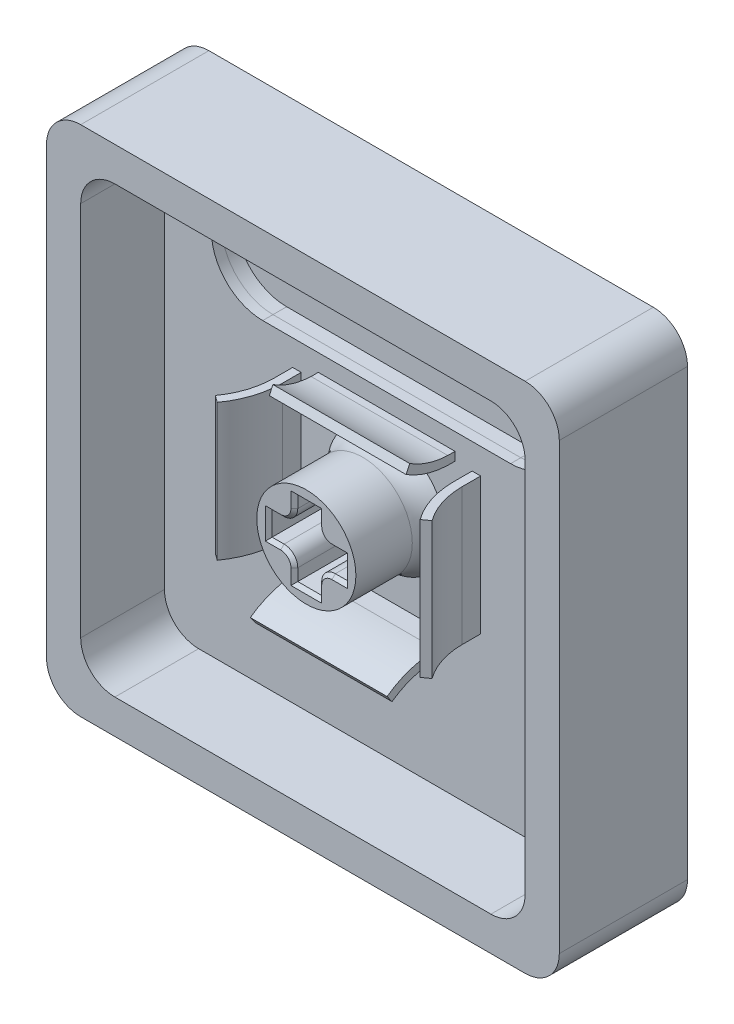
SolidWorks part; units mm, degrees
note: '?' marks a value the reader was unsure of. The reader was unsure of these and kept them because the rebuilt part matched: shared geometry of "草图1<6>", "草图1<7>".
other "标注1"
sketch "草图2" plane through (15, -15, 10) normal (0.3933, -0.7926, 0.466) x (0.9059, 0.4207, -0.0491)
ref_plane "前视基准面" through (0, 0, 0) normal (0, 0, 1) x (1, 0, 0)
ref_plane "上视基准面" through (0, 0, 0) normal (0, 1, 0) x (1, 0, 0)
ref_plane "右视基准面" through (0, 0, 0) normal (1, 0, 0) x (0, 0, -1)
sketch "草图1" plane through (0, 0, 0) normal (0, 0, 1) x (1, 0, 0)
  line L0 (-13, 15) -> (13, 15)
  line L1 (-11, 13) -> (11, 13)
  line L2 (-13, 11) -> (-13, -11)
  line L3 (-11, -13) -> (11, -13)
  line L4 (13, 11) -> (13, -11)
  line L5 (0, -13) -> (0, 13) construction
  line L6 (-13, 0) -> (13, 0) construction
  line L7 (15, 13) -> (15, -13)
  line L8 (-13, -15) -> (13, -15)
  line L9 (-15, 13) -> (-15, -13)
  line L10 (-13, -13) -> (13, -13) construction
  line L11 (-2.2, 0.7) -> (2.2, 0.7)
  line L12 (-2.2, 0.7) -> (-2.2, -0.7)
  line L13 (-2.2, -0.7) -> (2.2, -0.7)
  line L14 (2.2, 0.7) -> (2.2, -0.7)
  line L15 (0, -0.7) -> (0, 0.7) construction
  line L16 (-2.2, 0) -> (2.2, 0) construction
  line L17 (-0.7, 2.2) -> (0.7, 2.2)
  line L18 (-0.7, 2.2) -> (-0.7, -2.2)
  line L19 (-0.7, -2.2) -> (0.7, -2.2)
  line L20 (0.7, 2.2) -> (0.7, -2.2)
  line L21 (0, -2.2) -> (0, 2.2) construction
  line L22 (-0.7, 0) -> (0.7, 0) construction
  line L23 (13, 13) -> (13, -13) construction
  line L24 (-13, 13) -> (13, 13) construction
  line L25 (-13, 13) -> (-13, -13) construction
  line L26 (-15, 15) -> (-15, -15) construction
  line L27 (-15, -15) -> (15, -15) construction
  line L28 (15, 15) -> (15, -15) construction
  line L29 (-15, 15) -> (15, 15) construction
  line L36 (-13, 0) -> (-2.5, 0) construction
  circle A0 centre (0, 0) radius 2.9
  arc A1 (11, -13) -> (13, -11) centre (11, -11) ccw
  arc A2 (13, 11) -> (11, 13) centre (11, 11) ccw
  arc A3 (-13, 11) -> (-11, 13) centre (-11, 11) cw
  arc A4 (-13, -11) -> (-11, -13) centre (-11, -11) ccw
  arc A5 (-15, -13) -> (-13, -15) centre (-13, -13) ccw
  arc A6 (13, -15) -> (15, -13) centre (13, -13) ccw
  arc A7 (15, 13) -> (13, 15) centre (13, 13) ccw
  arc A8 (-15, 13) -> (-13, 15) centre (-13, 13) cw
  point P0 (0, 0)
  point P19 (13, -13)
  point P66 (0.0162, 0.0162)
  dimension "D4" = 5.8
  dimension "D9" = 2
  dimension "D1" = 30
  dimension "D2" = 30
  dimension "D5" = 4.4
  dimension "D6" = 1.4
  dimension "D7" = 4.4
  dimension "D8" = 1.4
  dimension "D3" = 2
extrude "凸台-拉伸1" add sketch "草图1" along normal blind 5.5 contours A8 L9 A5 L8 A6 L7 A7 L0 A4 L2 A3 L1 A2 L4 A1 L3
extrude "凸台-拉伸2" add sketch "草图1<6>" along normal blind 5.3 separate body contours A0 L17 L20 L11 L14 L13 L19 L18 L12
sketch "草图1<6>" plane through (0, 0, 0) normal (0, 0, 1) x (1, 0, 0) same geometry as "草图1"
extrude "凸台-拉伸3" add sketch "草图1<7>" against normal blind 2 contours L8 A6 L7 A7 L0 A8 L9 A5
sketch "草图1<7>" plane through (0, 0, 0) normal (0, 0, 1) x (1, 0, 0) same geometry as "草图1"
sketch "草图3" plane through (0, 0, 0) normal (0, 0, 1) x (1, 0, 0)
  line L8 (0.7, 0.7) -> (0.7, 2.2)
  line L10 (0.7, 0.7) -> (0.7, 2.2)
  line L15 (-0.7, 0.7) -> (-2.2, 0.7)
  line L16 (-2.2, 0.7) -> (-2.2, -0.7)
  line L17 (-2.2, -0.7) -> (-0.7, -0.7)
  line L19 (0.7, 2.2) -> (-0.7, 2.2)
  line L20 (0.7, 2.2) -> (-0.7, 2.2)
  line L21 (0.7, -0.7) -> (2.2, -0.7)
  line L22 (2.2, -0.7) -> (2.2, 0.7)
  line L23 (2.2, 0.7) -> (0.7, 0.7)
  line L27 (-0.7, 0.7) -> (-2.2, 0.7)
  line L28 (-2.2, 0.7) -> (-2.2, -0.7)
  line L29 (-2.2, -0.7) -> (-0.7, -0.7)
  line L33 (0.7, -0.7) -> (2.2, -0.7)
  line L34 (2.2, -0.7) -> (2.2, 0.7)
  line L35 (2.2, 0.7) -> (0.7, 0.7)
  line L36 (-0.7, 2.2) -> (-0.7, 0.7)
  line L37 (-0.7, 2.2) -> (-0.7, 0.7)
  line L38 (-0.7, -0.7) -> (-0.7, -2.2)
  line L39 (-0.7, -0.7) -> (-0.7, -2.2)
  line L40 (-0.7, -2.2) -> (0.7, -2.2)
  line L41 (-0.7, -2.2) -> (0.7, -2.2)
  line L42 (0.7, -2.2) -> (0.7, -0.7)
  line L43 (0.7, -2.2) -> (0.7, -0.7)
  dimension "D1" = 0
extrude "凸台-拉伸4" add sketch "草图3" along normal blind 2
sketch "草图5" plane through (0, 0, 0) normal (0, 0, 1) x (1, 0, 0)
  line L6 (7.25, 8.5) -> (-7.25, 8.5) construction
  line L7 (7.25, 5.5) -> (-7.25, 5.5)
  line L9 (7.25, 11.5) -> (-7.25, 11.5)
  line L10 (0, 0) -> (0, -50000) construction
  arc A0 (7.25, 5.5) -> (7.25, 11.5) centre (7.25, 8.5) ccw
  arc A1 (-7.25, 11.5) -> (-7.25, 5.5) centre (-7.25, 8.5) ccw
  point P2 (0, 8.5)
  dimension "D2" = 3
  dimension "D1" = 14.5
  dimension "D3" = 8.5
extrude "切除-拉伸1" cut sketch "草图5" against normal up to next
sketch "草图6" plane through (0, 0, -2) normal (0, 0, -1) x (-1, 0, 0)
  line L10 (7.25, 5.5) -> (-7.25, 5.5) construction
  line L11 (-7.25, 11.5) -> (7.25, 11.5) construction
  line L12 (7.25, 5.5) -> (-7.25, 5.5)
  line L13 (-7.25, 11.5) -> (7.25, 11.5)
  arc A0 (7.25, 5.5) -> (7.25, 11.5) centre (7.25, 8.5) ccw construction
  arc A1 (-7.25, 11.5) -> (-7.25, 5.5) centre (-7.25, 8.5) ccw construction
  arc A2 (7.25, 5.5) -> (7.25, 11.5) centre (7.25, 8.5) ccw
  arc A3 (-7.25, 11.5) -> (-7.25, 5.5) centre (-7.25, 8.5) ccw
extrude "凸台-拉伸6" add sketch "草图6" against normal blind 1.2 separate body
sketch "草图7" plane through (0, 0, 0) normal (0, 0, 1) x (1, 0, 0)
  line L0 (7.25, 5.5) -> (-7.25, 5.5) construction
  line L1 (7.25, 11.5) -> (-7.25, 11.5) construction
  line L2 (7.25, 5.5) -> (-7.25, 5.5)
  line L3 (7.25, 11.5) -> (-7.25, 11.5)
  line L4 (-13, 11) -> (-13, -11)
  line L5 (-11, -13) -> (11, -13)
  line L6 (13, -11) -> (13, 11)
  line L7 (11, 13) -> (-11, 13)
  line L8 (-13, 11) -> (-13, -11)
  line L9 (-11, -13) -> (11, -13)
  line L10 (13, -11) -> (13, 11)
  line L11 (11, 13) -> (-11, 13)
  circle A0 centre (0, 0) radius 2.9 construction
  circle A1 centre (0, 0) radius 2.9
  arc A2 (7.25, 5.5) -> (7.25, 11.5) centre (7.25, 8.5) ccw construction
  arc A3 (-7.25, 11.5) -> (-7.25, 5.5) centre (-7.25, 8.5) ccw construction
  arc A4 (-13, -11) -> (-11, -13) centre (-11, -11) ccw
  arc A5 (11, -13) -> (13, -11) centre (11, -11) ccw
  arc A6 (13, 11) -> (11, 13) centre (11, 11) ccw
  arc A7 (-11, 13) -> (-13, 11) centre (-11, 11) ccw
  arc A8 (-13, -11) -> (-11, -13) centre (-11, -11) ccw
  arc A9 (11, -13) -> (13, -11) centre (11, -11) ccw
  arc A10 (13, 11) -> (11, 13) centre (11, 11) ccw
  arc A11 (-11, 13) -> (-13, 11) centre (-11, 11) ccw
  arc A12 (7.25, 5.5) -> (7.25, 11.5) centre (7.25, 8.5) ccw
  arc A13 (-7.25, 11.5) -> (-7.25, 5.5) centre (-7.25, 8.5) ccw
  dimension "D1" = 0
ref_plane "基准面1" through (0, 0, 0) normal (0, 1, 0) x (1, 0, 0)
ref_axis "基准轴1" through (0, 0, 5.3) along (0, 0, -1)?
sketch "草图9" plane through (0, 0, 0) normal (0, 1, 0) x (1, 0, 0)
  line L0 (-15, 1.1634) -> (15, 1.1634) construction
  line L4 (15, -5.5) -> (13, -5.5)
  line L6 (15, -5.5) -> (13, -5.5) construction
  line L12 (13, -5.5) -> (-13, -5.5)
  line L14 (13, -5.5) -> (-13, -5.5) construction
  line L16 (-13, -5.5) -> (-15, -5.5)
  line L18 (-13, -5.5) -> (-15, -5.5) construction
  line L20 (5.9352, -4.5764) -> (6.3407, -4.2839)
  line L21 (5.5, 1.1634) -> (5.5, -1.6819)
  line L22 (5, 1.1634) -> (5, -1.6819)
  line L23 (0, 0) -> (0, 50000) construction
  line L24 (5.5, 1.1634) -> (5, 1.1634)
  line L29 (-15, -5.5) -> (-15, 2)
  line L30 (-15, -5.5) -> (-15, 2) construction
  line L31 (-15, 2) -> (-13, 2)
  line L32 (-15, 2) -> (-13, 2) construction
  line L33 (-13, 2) -> (13, 2)
  line L34 (-13, 2) -> (13, 2) construction
  line L35 (13, 2) -> (15, 2)
  line L36 (13, 2) -> (15, 2) construction
  line L37 (15, 2) -> (15, -5.5)
  line L38 (15, 2) -> (15, -5.5) construction
  arc A0 (5.5, -1.6819) -> (6.3407, -4.2839) centre (9.9471, -1.6819) ccw
  arc A1 (5, -1.6819) -> (5.9352, -4.5764) centre (9.9471, -1.6819) ccw
  point P41 (0, 1.1634)
  dimension "D1" = 0.5
  dimension "D2" = 0.5
  dimension "D3" = 5
extrude "凸台-拉伸9" add sketch "草图9" along normal mid plane 8 separate body
ref_plane "基准面4" through (0, 0, 0) normal (-1, 0, 0) x (0, 0, 1)
sketch "草图12" plane through (0, 0, 0) normal (-1, 0, 0) x (0, 0, 1)
  line L0 (1.0216, 4.5) -> (1.0216, 4) construction
  line L1 (-1.1634, 4.5) -> (-1.1634, 4)
  line L6 (0, 0) -> (-50000, 0) construction
  line L7 (1.0216, 4.5) -> (-1.1634, 4.5)
  line L8 (-1.1634, 4) -> (1.0216, 4)
  line L9 (3.4655, 4.7548) -> (3.252, 5.2069)
  arc A4 (3.252, 5.2069) -> (1.0216, 4.5) centre (0.8405, 8.9434) cw
  arc A5 (3.4655, 4.7548) -> (1.0216, 4) centre (0.8334, 8.9435) cw
  point P0 (3.252, 5.2069)
  dimension "D1" = 0.5
  dimension "D4" = 0.5
  dimension "D7" = 4
extrude "凸台-拉伸13" add sketch "草图12" along normal mid plane 8 separate body
ref_plane "基准面3" through (0, 0, 0) normal (-0.7071, 0.7071, 0) x (0.7071, 0.7071, 0)
sketch "草图11" plane through (0, 0, 0) normal (-0.7071, 0.7071, 0) x (0.7071, 0.7071, 0)
  line L0 (13.4246, 2) -> (20.3848, 2) construction
  line L1 (20.3848, 2) -> (20.3848, -5.5) construction
  line L2 (20.3848, -5.5) -> (17.5563, -5.5) construction
  line L3 (17.5563, -5.5) -> (16.9706, -5.5) construction
  line L4 (16.9706, -5.5) -> (1.4142, -5.5) construction
  line L5 (1.4142, -5.5) -> (-1.4142, -5.5) construction
  line L6 (-1.4142, -5.5) -> (-16.9706, -5.5) construction
  line L7 (-16.9706, -5.5) -> (-17.5563, -5.5) construction
  line L8 (-17.5563, -5.5) -> (-20.3848, -5.5) construction
  line L9 (-20.3848, -5.5) -> (-20.3848, 2) construction
  line L10 (-20.3848, 2) -> (6.364, 2) construction
  line L11 (6.364, 2) -> (12.5511, 2) construction
  line L12 (12.5511, 2) -> (13.4246, 2) construction
  line L13 (14.3563, -0.0135) -> (14.3563, -0.6104)
  line L14 (15.5563, 0) -> (15.5563, -0.6104)
  line L15 (14.3563, -0.6104) -> (15.5563, -0.6104) construction
  line L17 (14.3563, -0.0135) -> (15.5563, 0)
  line L18 (15.5563, -0.6104) -> (15.5563, -2.2135)
  line L19 (15.5563, -2.2135) -> (12.7123, -2.2135)
  line L20 (12.7123, -2.2135) -> (12.7123, -1.0135)
  line L21 (12.7123, -1.0135) -> (14.3563, -1.0135)
  line L22 (14.3563, -1.0135) -> (14.3563, -0.6104)
  dimension "D1" = 1.2
  dimension "D2" = 1.2
  dimension "D3" = 1
extrude "凸台-拉伸11" [suppressed] add sketch "草图11" along normal mid plane 2 separate body
fillet "圆角4" radius 0.8 4 edges at (-0.7, 0.7, 3.65) (0.7, 0.7, 3.65) (-0.7, -0.7, 3.65) (0.7, -0.7, 3.65)
chamfer "倒角1" distance 0.2 angle 45 16 edges at (-0.7, 1.85, 5.3) (-1.85, 0.7, 5.3) (-1.85, -0.7, 5.3) (-0.7, -1.85, 5.3) (0, -2.2, 5.3) (0.7, -1.85, 5.3) (1.85, -0.7, 5.3) (1.85, 0.7, 5.3) (0.7, 1.85, 5.3) (0, 2.2, 5.3) (-0.9343, -0.9343, 5.3) (0.9343, -0.9343, 5.3) (0.9343, 0.9343, 5.3) (-0.9343, 0.9343, 5.3) (-2.2, 0, 5.3) (2.2, 0, 5.3)
fillet "圆角5" radius 2 1 edges at (2.9, 0, 0)
sketch "草图10" plane through (0, 0, 0) normal (0, 0, 1) x (1, 0, 0)
  line L0 (7.25, 5.5) -> (-7.25, 5.5) construction
  line L1 (7.25, 11.5) -> (-7.25, 11.5) construction
  line L2 (7.25, 5.5) -> (-7.25, 5.5)
  line L3 (7.25, 11.5) -> (-7.25, 11.5)
  line L4 (-13, 11) -> (-13, -11)
  line L5 (-11, -13) -> (11, -13)
  line L6 (13, -11) -> (13, 11)
  line L7 (11, 13) -> (-11, 13)
  line L8 (-13, 11) -> (-13, -11)
  line L9 (-11, -13) -> (11, -13)
  line L10 (13, -11) -> (13, 11)
  line L11 (11, 13) -> (-11, 13)
  arc A0 (7.25, 5.5) -> (7.25, 11.5) centre (7.25, 8.5) ccw construction
  arc A1 (-7.25, 11.5) -> (-7.25, 5.5) centre (-7.25, 8.5) ccw construction
  arc A2 (7.25, 5.5) -> (7.25, 11.5) centre (7.25, 8.5) ccw
  arc A3 (-7.25, 11.5) -> (-7.25, 5.5) centre (-7.25, 8.5) ccw
  arc A4 (-13, -11) -> (-11, -13) centre (-11, -11) ccw
  arc A5 (11, -13) -> (13, -11) centre (11, -11) ccw
  arc A6 (13, 11) -> (11, 13) centre (11, 11) ccw
  arc A7 (-11, 13) -> (-13, 11) centre (-11, 11) ccw
  arc A8 (-13, -11) -> (-11, -13) centre (-11, -11) ccw
  arc A9 (11, -13) -> (13, -11) centre (11, -11) ccw
  arc A10 (13, 11) -> (11, 13) centre (11, 11) ccw
  arc A11 (-11, 13) -> (-13, 11) centre (-11, 11) ccw
  dimension "D1" = 0
extrude "凸台-拉伸10" add sketch "草图10" along normal blind 0.6 separate body
pattern_circular "阵列(圆周)6" count 3 every 90 about axis through (0, 0, 0) along (0, 0, 1) of bodies 120
